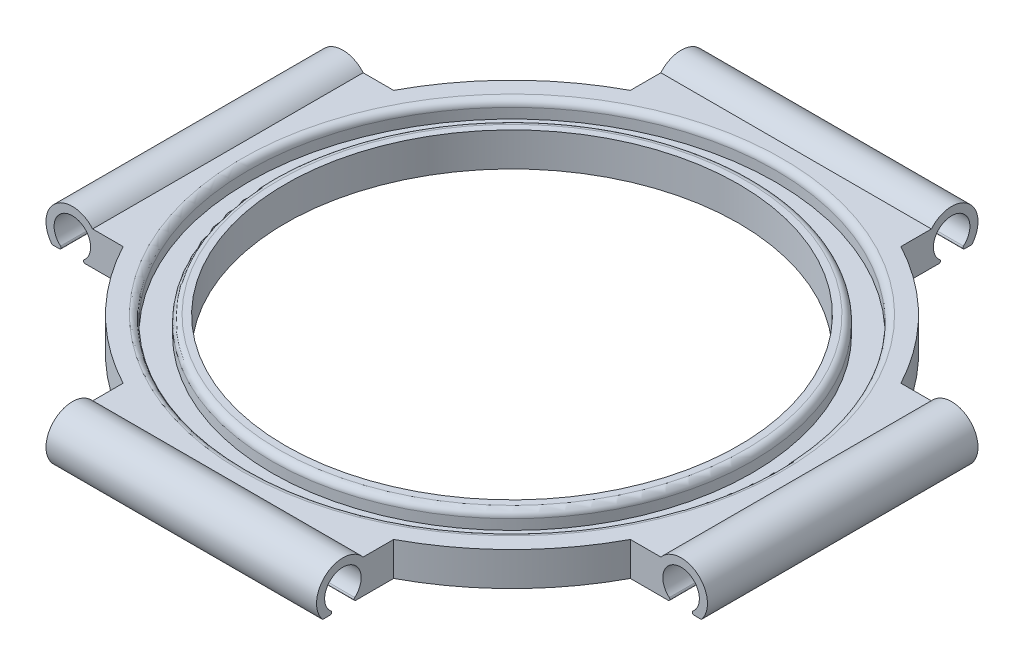
SolidWorks part; units mm, degrees
note: The reader was unsure of these and kept them because the rebuilt part matched: shared geometry of "Эскиз13<3>".
ref_plane "Front Plane" through (0, 0, 0) normal (0, 0, 1) x (1, 0, 0)
ref_plane "Top Plane" through (0, 0, 0) normal (0, 1, 0) x (1, 0, 0)
ref_plane "Right Plane" through (0, 0, 0) normal (1, 0, 0) x (0, 0, -1)
sketch "Эскиз2" plane through (0, 0, 0) normal (0, 1, 0) x (1, 0, 0)
  circle A0 centre (0, 0) radius 33.5
  circle A1 centre (0, 0) radius 42.5
  dimension "D1" = 67
  dimension "D2" = 85
extrude "Бобышка-Вытянуть1" add sketch "Эскиз2" along normal blind 5
ref_plane "Плоскость1" through (0, 0, 49) normal (0, 0, 1) x (1, 0, 0)
sketch "Эскиз3" plane through (0, 0, 49) normal (0, 0, 1) x (1, 0, 0)
  line L0 (-20, 0) -> (20, 0)
  line L2 (-20, 0) -> (-20, 5)
  line L3 (42.5, 5) -> (-42.5, 5) construction
  line L4 (-20, 5) -> (20, 5)
  line L5 (20, 5) -> (20, 0)
  point P3 (0, 0)
  dimension "D1" = 40
extrude "Бобышка-Вытянуть2" add sketch "Эскиз3" against normal up to surface (11.5 mm away)
sketch "Эскиз6" plane through (0, 5, 0) normal (0, 1, 0) x (1, 0, 0)
  circle A0 centre (0, 0) radius 35.5
  circle A1 centre (0, 0) radius 39
  point P0 (0, 0)
  dimension "D1" = 71
  dimension "D2" = 78
sketch "Эскиз7" plane through (0, 0, 0) normal (0, 0, 1) x (1, 0, 0)
  line L0 (0, 0) -> (0, 16.4553) construction
ref_plane "Плоскость2" through (0, 5, 0) normal (0, 1, 0) x (1, 0, 0)
sketch "Эскиз8" plane through (0, 5, 0) normal (0, 1, 0) x (1, 0, 0)
  line L1 (-20, -50) -> (20, -50)
  line L2 (-20, -50) -> (-20, -40)
  line L3 (-20, -40) -> (20, -40)
  line L4 (20, -50) -> (20, -40)
  line L5 (0, -40) -> (0, -50) construction
  line L6 (0, 0) -> (0, -53.8197) construction
  point P5 (0, -45)
  point P8 (0, -40)
  dimension "D1" = 10
  dimension "D2" = 45
  dimension "D3" = 40
sketch "Эскиз13" plane through (20, 0, 0) normal (1, 0, 0) x (0, 0, -1)
  line L0 (1.1636, -1.2078) -> (0, 0) construction
  line L1 (0, 2.5) -> (-45, 2.5) construction
  line L3 (0, 0) -> (0, 16.4553) construction
  line L4 (-45, 5) -> (-45, 2.5) construction
  line L6 (-40, 5) -> (-50, 5) construction
  line L7 (-45, 2.5) -> (-45, 0) construction
  line L8 (-37.5, 0) -> (-49, 0) construction
  line L9 (-46.8, 0.4875) -> (-45, 0.4875) construction
  line L10 (-46.8, 0.4875) -> (-43.2, 0.4875)
  circle A0 centre (-45, 2.5) radius 2.7
  circle A1 centre (-45, 2.5) radius 3.9
  arc A2 (-43.2, 0.4875) -> (-42.0067, 0) centre (-43.2, -1.2167) cw
  arc A3 (-46.8, 0.4875) -> (-47.9933, 0) centre (-46.8, -1.2167) ccw
  point P22 (-43.9802, 0)
  point P23 (-46.0198, 0)
  line M6 (-49, 0) -> (-37.5, 0)
  line M8 (-37.5, 5) -> (-49, 5)
  line M9 (-49, 5) -> (-49, 0)
  dimension "D2" = 7.8
  dimension "D3" = 5.4
  dimension "D5" = 1.7042
  dimension "D6" = 1.7042
  dimension "D1" = 45
  dimension "D4" = 1.8
extrude "Бобышка-Вытянуть4" add sketch "Эскиз13" against normal blind 40 contours A3 A0 A1 M8 | A1 A0 M8 | A0 A2 A1 M8 | A0 M8
extrude "Вырез-Вытянуть4" cut sketch "Эскиз13<3>" against normal blind 40 contours A0 L10 M8 | A0 M8 | L10 A0 M6 | A1 M8 M9 M6
sketch "Эскиз13<3>" plane through (20, 0, 0) normal (1, 0, 0) x (0, 0, -1) same geometry as "Эскиз13"
fillet "Скругление2" radius 0.25 1 edges at (0, 0, 43.9802)
pattern_circular "Круговой массив16" count 4 over 360 about axis through (0, 0, 0) along (0, 1, 0) of "Скругление2", "Вырез-Вытянуть4", "Бобышка-Вытянуть4", "Бобышка-Вытянуть2"
extrude "Вырез-Вытянуть5" cut sketch "Эскиз6" against normal blind 2.5
fillet "Скругление3" radius 1 2 edges at (0, 5, 39) (0, 5, 35.5)
